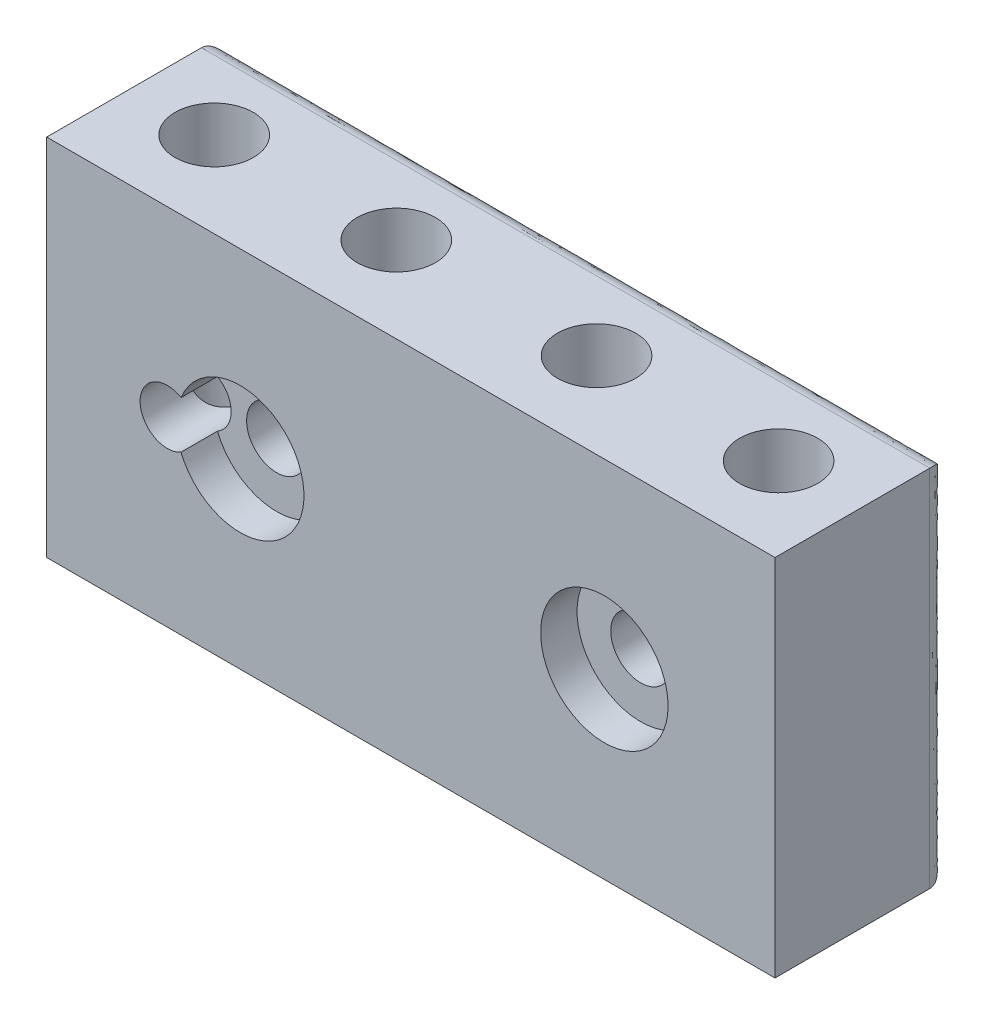
SolidWorks part; units mm, degrees
material "petg 20%"
ref_plane "Front Plane" through (0, 0, 0) normal (0, 0, 1) x (1, 0, 0)
ref_plane "Top Plane" through (0, 0, 0) normal (0, 1, 0) x (1, 0, 0)
ref_plane "Right Plane" through (0, 0, 0) normal (1, 0, 0) x (0, 0, -1)
sketch "Sketch1" plane through (0, 0, 0) normal (0, 0, 1) x (1, 0, 0)
  line L1 (20, 10) -> (-20, 10)
  line L2 (20, 10) -> (20, -10)
  line L3 (20, -10) -> (-20, -10)
  line L4 (-20, 10) -> (-20, -10)
  line L5 (20, 10) -> (-20, -10) construction
  line L6 (20, -10) -> (-20, 10) construction
  point P0 (0, 0)
  dimension "D1" = 40
  dimension "D2" = 20
extrude "Boss-Extrude1" add sketch "Sketch1" along normal blind 9.5
sketch "Sketch3" plane through (0, 0, 0) normal (0, 0, -1) x (-1, 0, 0)
  line L0 (13.3714, -3.45) -> (1.3714, -3.45)
  line L1 (13.3714, 3.45) -> (1.3714, 3.45)
  line L2 (-10.6286, 0) -> (9.9214, 0) construction
  arc A0 (-6.4266, 6.3327) -> (-6.4266, -6.3327) centre (-10.6286, 0) ccw
  arc A1 (13.3714, -3.45) -> (13.3714, 3.45) centre (13.3714, 0) ccw
  spline S0 degree 2 poles (-6.4266, -6.3327) (-3.0128, -3.5547) (1.3714, -3.45) knots 0 0 0 1 1 1
  spline S1 degree 2 poles (-6.4266, 6.3327) (-3.0128, 3.5547) (1.3714, 3.45) knots 0 0 0 1 1 1
  dimension "D1" = 15.2
  dimension "D2" = 6.9
extrude "Cut-Extrude1" cut sketch "Sketch3" against normal blind 2
fillet "Fillet1" radius 1 4 edges at (-20, 0, 0) (0, -10, 0) (0, 10, 0) (20, 0, 0) first distance on face at (-1.3801, -0.4805, 0)
sketch "Sketch4" plane through (0, 10, 0) normal (0, 1, 0) x (1, 0, 0)
  circle A0 centre (-15.5, -4.8) radius 2.15
  circle A1 centre (-5.5, -4.8) radius 2.15
  circle A2 centre (5.5, -4.8) radius 2.15
  circle A3 centre (15.5, -4.8) radius 2.15
  dimension "D1" = 4.3
  dimension "D2" = 4.3
  dimension "D3" = 4.3
  dimension "D4" = 4.3
extrude "Cut-Extrude2" cut sketch "Sketch4" against normal through all
sketch "Sketch5" plane through (0, 0, 0) normal (0, 0, -1) x (-1, 0, 0)
  circle A0 centre (13.3714, 0) radius 1.5
  circle A1 centre (9.3714, 0) radius 1.65
  circle A2 centre (-10.6286, 0) radius 1.65
  dimension "D1" = 3.3
  dimension "D2" = 3
  dimension "D3" = 4
  dimension "D4" = 3.3
extrude "Cut-Extrude3" cut sketch "Sketch5" against normal through all
sketch "Sketch6" plane through (0, 0, 9.5) normal (0, 0, 1) x (1, 0, 0)
  circle A0 centre (10.6286, 0) radius 3.5
  circle A1 centre (-9.3714, 0) radius 3.5
  dimension "D1" = 7
  dimension "D2" = 7
extrude "Cut-Extrude4" cut sketch "Sketch6" against normal blind 2
